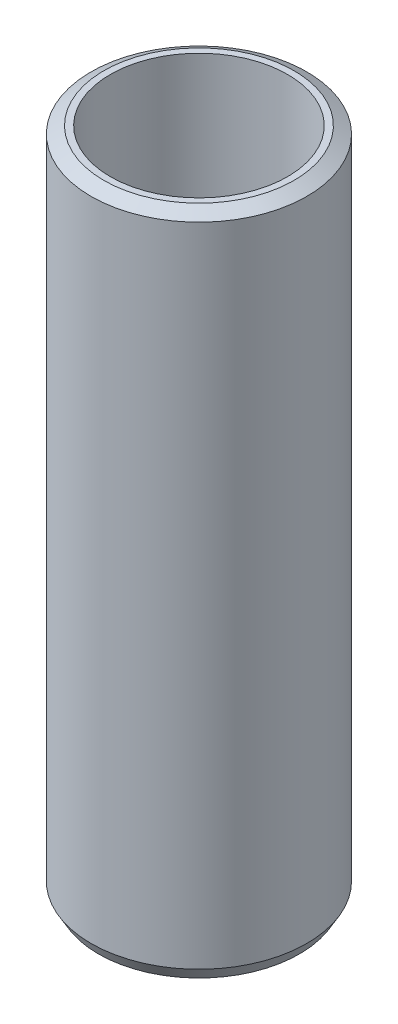
SolidWorks part; units mm, degrees
ref_plane "Front Plane" through (0, 0, 0) normal (0, 0, 1) x (1, 0, 0)
ref_plane "Top Plane" through (0, 0, 0) normal (0, 1, 0) x (1, 0, 0)
ref_plane "Right Plane" through (0, 0, 0) normal (1, 0, 0) x (0, 0, -1)
sketch "Sketch1" plane through (0, 0, 0) normal (0, 1, 0) x (1, 0, 0)
  circle A0 centre (0, 0) radius 45
  dimension "SHAFT_OD" = 90
extrude "Boss-Extrude1" add sketch "Sketch1" along normal blind 278.2284
sketch "Sketch2" plane through (0, 0, 0) normal (0, 1, 0) x (1, 0, 0)
  circle A0 centre (0, 0) radius 36.957
  dimension "BORE_D" = 73.914
extrude "Cut-Extrude1" cut sketch "Sketch2" along normal through all
chamfer "Chamfer1" distance 3.0873 angle 60 2 edges at (0, 278.2284, 45) (0, 0, 45) first distance on face at (0, 278.2284, 45) first distance on face at (0, 0, 36.957)
